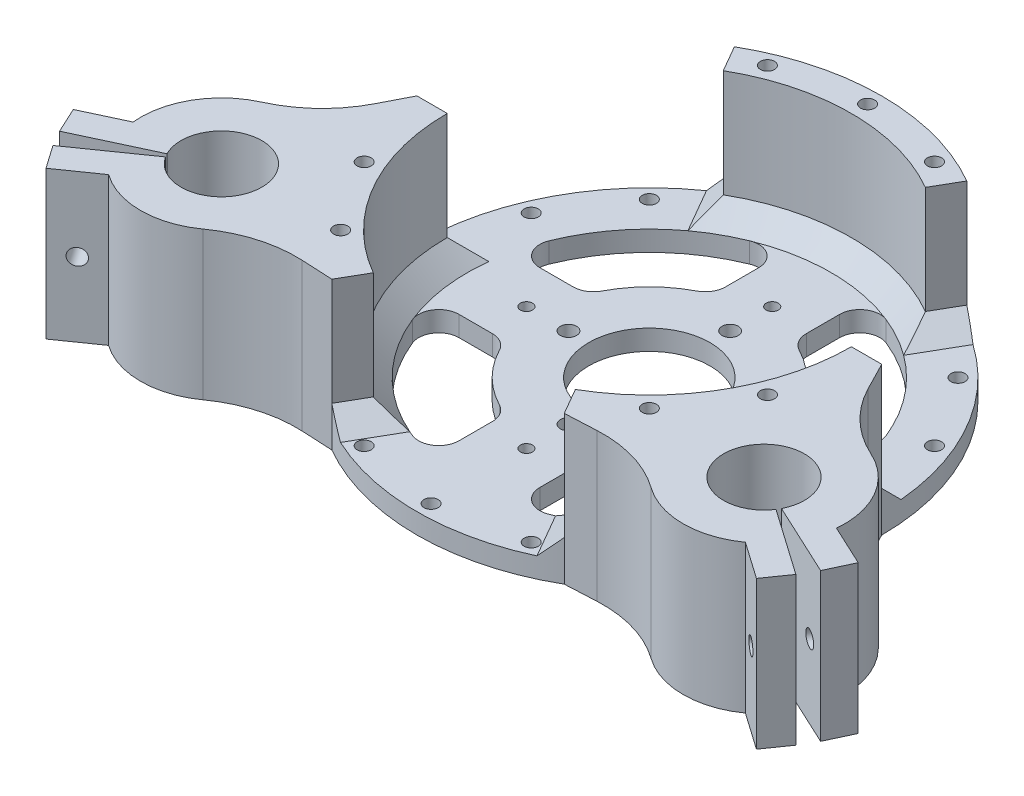
SolidWorks part; units mm, degrees
ref_plane "Front Plane" through (0, 0, 0) normal (0, 0, 1) x (1, 0, 0)
ref_plane "Top Plane" through (0, 0, 0) normal (0, 1, 0) x (1, 0, 0)
ref_plane "Right Plane" through (0, 0, 0) normal (1, 0, 0) x (0, 0, -1)
sketch "Sketch1" plane through (0, 0, 0) normal (0, 1, 0) x (1, 0, 0)
  circle A0 centre (0, 0) radius 57.5
  dimension "D1" = 115
extrude "Boss-Extrude1" add sketch "Sketch1" along normal blind 36.6
sketch "Sketch2" plane through (0, 36.6, 0) normal (0, 1, 0) x (1, 0, 0)
  circle A0 centre (0, 0) radius 50
  dimension "D1" = 100
extrude "Cut-Extrude1" cut sketch "Sketch2" against normal blind 31.6
sketch "Sketch3" plane through (0, 0, 0) normal (0, -1, 0) x (1, 0, 0)
  line L0 (0, 62.4892) -> (0, -59.6631) construction
  line L1 (-72.2237, 0) -> (67.9845, 0) construction
  line L6 (43.8748, 10) -> (43.8748, -10)
  line L7 (43.8748, 10) -> (25.6174, 10)
  line L8 (43.8748, -10) -> (25.6174, -10)
  line L9 (25.6174, 10) -> (25.6174, -10)
  line L10 (-10, -43.8748) -> (10, -43.8748)
  line L11 (-10, -43.8748) -> (-10, -25.6174)
  line L12 (10, -43.8748) -> (10, -25.6174)
  line L13 (-10, -25.6174) -> (10, -25.6174)
  line L14 (-43.8748, 10) -> (-43.8748, -10)
  line L15 (-43.8748, 10) -> (-25.6174, 10)
  line L16 (-43.8748, -10) -> (-25.6174, -10)
  line L17 (-25.6174, 10) -> (-25.6174, -10)
  line L18 (-10, 43.8748) -> (10, 43.8748)
  line L19 (-10, 43.8748) -> (-10, 25.6174)
  line L20 (10, 43.8748) -> (10, 25.6174)
  line L21 (-10, 25.6174) -> (10, 25.6174)
  circle A0 centre (0, 0) radius 20 construction
  circle A1 centre (0, 0) radius 15
  circle A2 centre (0, 20) radius 2
  circle A3 centre (20, 0) radius 2
  circle A4 centre (0, -20) radius 2
  circle A5 centre (-20, 0) radius 2
  circle A6 centre (0, 0) radius 27.5
  circle A7 centre (0, 0) radius 45
  point P15 (0, 0)
  dimension "D1" = 40
  dimension "D2" = 30
  dimension "D3" = 4
  dimension "D5" = 55
  dimension "D6" = 90
  dimension "D7" = 20
  dimension "D4" = 4
extrude "Cut-Extrude2" cut sketch "Sketch3" against normal blind 31.8 contours L19 A7 L15 A6 | L7 A7 L20 A6 | L12 A7 L8 A6 | L16 A7 L11 A6 | A5 | A1 | A2 | A3 | A4 region at (25.2593, 0, 25.2593) region at (25.2593, 0, -25.2593) region at (-25.2593, 0, 25.2593) region at (-25.2593, 0, -25.2593) region at (0, 0, 0) region at (0, 0, 20) region at (20, 0, 0) region at (0, 0, -20) region at (-20, 0, 0)
sketch "Sketch4" plane through (0, 0, 0) normal (0, -1, 0) x (1, 0, 0)
  line L0 (0, 0) -> (0, 54) construction
  line L1 (30.4056, 0) -> (0, 30.4056) construction
  line L2 (0, 30.4056) -> (-30.4056, 0) construction
  line L3 (-30.4056, 0) -> (0, -30.4056) construction
  line L4 (0, -30.4056) -> (30.4056, 0) construction
  line L5 (0, 0) -> (69.7116, 0) construction
  line L6 (0, 0) -> (0, 54) construction
  circle A0 centre (0, 0) radius 54 construction
  circle A13 centre (0, 0) radius 21.5 construction
  circle A14 centre (0, 30.4056) radius 1.5
  circle A15 centre (30.4056, 0) radius 1.5
  circle A16 centre (0, -30.4056) radius 1.5
  circle A17 centre (-30.4056, 0) radius 1.5
  circle A22 centre (0, 54) radius 1.75
  circle A38 centre (0, -54) radius 1.75 [skipped]
  circle A39 centre (20.6649, 49.8895) radius 1.75
  circle A40 centre (38.1838, 38.1838) radius 1.75
  circle A41 centre (49.8895, 20.6649) radius 1.75
  circle A44 centre (49.8895, -20.6649) radius 1.75
  circle A45 centre (38.1838, -38.1838) radius 1.75
  circle A46 centre (20.6649, -49.8895) radius 1.75
  circle A47 centre (0, -54) radius 1.75
  circle A48 centre (-20.6649, -49.8895) radius 1.75
  circle A49 centre (-38.1838, -38.1838) radius 1.75
  circle A50 centre (-49.8895, -20.6649) radius 1.75
  circle A52 centre (-49.8895, 20.6649) radius 1.75
  circle A53 centre (-38.1838, 38.1838) radius 1.75
  circle A54 centre (-20.6649, 49.8895) radius 1.75
  circle A55 centre (-54, 0) radius 1.75 [skipped]
  circle A56 centre (54, 0) radius 1.75 [skipped]
  point P29 (0, 0)
  point P43 (0, 0)
  point P53 (0, 0)
  point P54 (0, 0)
  dimension "D1" = 108
  dimension "D2" = 0
  dimension "D5" = 3
  dimension "D8" = 16
  dimension "D3" = 3.5
  dimension "D4" = 43
  dimension "D7" = 2
  dimension "D6" = 4
extrude "Cut-Extrude3" cut sketch "Sketch4" against normal blind 50
sketch "Sketch5" plane through (0, 36.6, 0) normal (0, 1, 0) x (1, 0, 0)
  line L0 (0, -57.5) -> (0, 0) construction
  line L1 (0, 0) -> (-28.75, -49.7965) construction
  line L2 (0, 0) -> (28.75, -49.7965) construction
  line L3 (0, 0) -> (-28.75, -49.7965)
  line L4 (0, 0) -> (28.75, -49.7965)
  circle A0 centre (0, 0) radius 57.5 construction
  arc A1 (-28.75, -49.7965) -> (28.75, -49.7965) centre (0, 0) ccw
  dimension "D1" = 30
  dimension "D2" = 30
extrude "Cut-Extrude4" cut sketch "Sketch5" against normal up to surface (31.6 mm away) up to face at (0, 5, 31.9056)
pattern_circular "CirPattern1" count 3 over 360 about axis through (0, 5, 0) along (0, 1, 0) of "Cut-Extrude4" reverse direction yes
fillet "Fillet2" radius 5 16 edges at (-25.6174, 2.5, 10) (-10, 2.5, 25.6174) (-10, 2.5, 43.8748) (-43.8748, 2.5, 10) (43.8748, 2.5, 10) (25.6174, 2.5, 10) (10, 2.5, 25.6174) (10, 2.5, 43.8748) (10, 2.5, -25.6174) (25.6174, 2.5, -10) (43.8748, 2.5, -10) (10, 2.5, -43.8748) (-25.6174, 2.5, -10) (-10, 2.5, -25.6174) (-10, 2.5, -43.8748) (-43.8748, 2.5, -10)
sketch "Sketch6" plane through (0, 36.6, 0) normal (0, 1, 0) x (1, 0, 0)
  line L0 (0, 0) -> (67.117, -38.75) construction
  line L1 (0, 0) -> (84.7844, 0) construction
  line L2 (67.117, -38.75) -> (92.4201, -53.3588) construction
  line L3 (75.5165, -44.1766) -> (91.8995, -55.6482)
  line L4 (91.8995, -55.6482) -> (87.8845, -61.3822)
  line L5 (87.8845, -61.3822) -> (78.773, -55.0023)
  line L6 (76.0163, -43.3109) -> (94.1425, -51.7632)
  line L7 (94.1425, -51.7632) -> (97.1008, -45.4191)
  line L8 (97.1008, -45.4191) -> (87.0199, -40.7183)
  line L9 (57.5, 0) -> (67.117, -18.75)
  line L10 (67.117, -18.75) -> (49.7965, -48.75) construction
  line L11 (49.7965, -48.75) -> (28.75, -49.7965)
  circle A0 centre (67.117, -38.75) radius 10
  circle A1 centre (67.117, -38.75) radius 20
  arc A2 (28.75, -49.7965) -> (57.5, 0) centre (0, 0) ccw construction
  circle A3 centre (0, 0) radius 57.5
  point P9 (75.7772, -43.75)
  arc M8 (28.75, -49.7965) -> (57.5, 0) centre (0, 0) ccw
  dimension "D2" = 20
  dimension "D3" = 40
  dimension "D1" = 30
  dimension "D4" = 7
  dimension "D5" = 20
  dimension "D6" = 5
  dimension "D7" = 5
  dimension "D8" = 0.5
chamfer "Chamfer1" distance 5 angle 45 9 edges at (53.75, 5, 0) (43.3013, 5, 25) (26.875, 5, 46.5489) (-26.875, 5, -46.5489) (0, 5, -50) (26.875, 5, -46.5489) (-26.875, 5, 46.5489) (-43.3013, 5, 25) (-53.75, 5, 0)
extrude "Boss-Extrude2" add sketch "Sketch6" against normal up to surface (36.6 mm away) contours A1 L11 M8 | A1 L9 M8 | A1 L3 A0 L6 | A1 L6 L7 L8 | A1 L5 L4 L3 region at (79.2892, 36.6, 47.5089) region at (85.614, 36.6, 55.5967) region at (90.9552, 36.6, 46.3455) region at (42.0419, 36.6, 44.1701) region at (59.2734, 36.6, 14.3243) up to face at (0, 0, 52.25)
fillet "Fillet3" radius 30 2 edges at (67.117, 18.3, 18.75) (49.7965, 18.3, 48.75)
sketch "Sketch7" plane through (-0.0537, 0, 0.1152) normal (0.4226, 0, -0.9063) x (-0.9063, 0, -0.4226)
  line L0 (-101.6366, 0) -> (-101.6366, 36.6) construction
  line L1 (-96.0751, 0) -> (-107.1981, 0) construction
  line L2 (-107.1981, 36.6) -> (-96.0751, 36.6) construction
  circle A0 centre (-101.6366, 18.3) radius 2
  dimension "D1" = 4
extrude "Cut-Extrude5" cut sketch "Sketch7" against normal blind 10
sketch "Sketch8" plane through (0.0729, 0, -0.1041) normal (-0.5736, 0, 0.8192) x (0.8192, 0, 0.5736)
  line L0 (101.6366, 0) -> (101.6366, 36.6) construction
  line L1 (96.0751, 0) -> (107.1981, 0) construction
  line L2 (107.1981, 36.6) -> (96.0751, 36.6) construction
  circle A0 centre (101.6366, 18.3) radius 2
  dimension "D1" = 4
extrude "Cut-Extrude6" cut sketch "Sketch8" against normal blind 10
mirror "Mirror1" about plane through (0, 0, 0) normal (1, 0, 0) of "Cut-Extrude6", "Cut-Extrude5", "Fillet3", "Boss-Extrude2"
